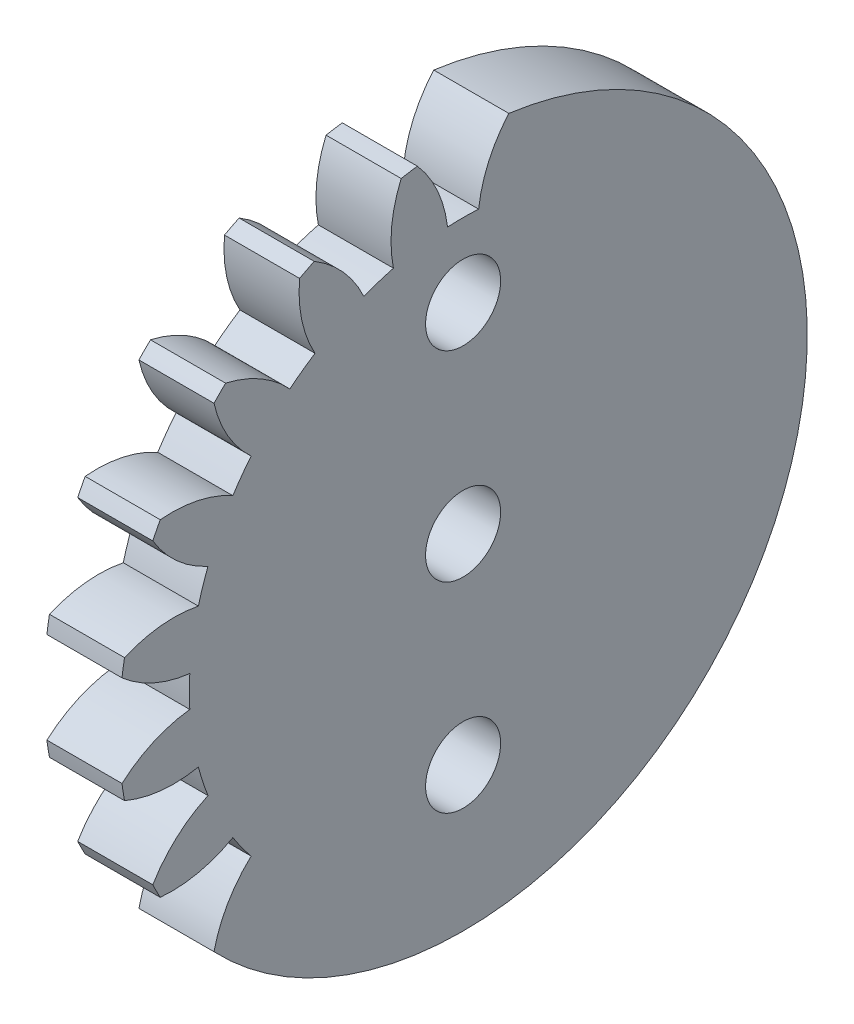
SolidWorks part; units mm, degrees
ref_plane "Plane1" through (0, 0, 0) normal (0, 0, 1) x (1, 0, 0)
ref_plane "Plane2" through (0, 0, 0) normal (0, 1, 0) x (1, 0, 0)
ref_plane "Plane3" through (0, 0, 0) normal (1, 0, 0) x (0, 0, -1)
sketch "HoldingSke" plane through (0, 0, 0) normal (0, 1, 0) x (1, 0, 0)
  line L0 (0, 0) -> (0.7518, -0.2736)
  line L1 (-15, 0) -> (100, 0) construction
  line L2 (0, 0) -> (-2.1039, 2.3779)
  line L3 (0, 0) -> (-11.863, 4.5341)
  line L4 (0, 0) -> (8.1152, 2.9537)
  line L5 (0, 0) -> (-46.8476, -17.4728)
  line L6 (0, 0) -> (-9.9476, -6.7116)
  line L7 (-2.1039, 2.3779) -> (8.6586, 51.2059)
  line L8 (-76.2, 54.61) -> (-75.7, 54.61)
  line L9 (-71.009, 38.7566) -> (-53.1078, 45.2721)
  line L10 (-76.2, 71.12) -> (104.1128, 71.12)
  line L11 (0, 0) -> (-12, 0)
  line L12 (-76.2, 101.6) -> (-76.155, 101.6)
  line L13 (24.9733, 27.94) -> (52.9518, 28.4284)
  line L14 (24.9733, 27.94) -> (24.9743, 27.94)
  line L15 (24.9733, 27.94) -> (100.4006, 29.5858)
  line L16 (-63.627, -1.25) -> (-12.827, -1.25)
  circle A0 centre (0, 0) radius 1.5
  circle A1 centre (0, 0) radius 10.9365
  circle A2 centre (0, 0) radius 37.5
  circle A3 centre (0, 0) radius 1.5
  dimension "Num_teeth" = 20
  dimension "Pitch_radius" = 180.3128
  dimension "Width" = 12
sketch "BasProSke" plane through (0, 0, 0) normal (0, 1, 0) x (1, 0, 0)
  line L0 (-10, 0) -> (60, 0) construction
  line L1 (0, 0) -> (0, 13.75)
  line L2 (0, 0) -> (3, 0)
  line L3 (3, 0) -> (3, 13.75)
  line L4 (3, 13.75) -> (0, 13.75)
  dimension "Thickness" = 3
  dimension "Diameter" = 27.5
revolve "Base-Revolve" add sketch "BasProSke" angle 360 about L0
sketch "TooCutSke" plane through (0, 0, 0) normal (1, 0, 0) x (0, 0, -1)
  line L1 (0, 0) -> (0, 107) construction
  line L2 (0, 0) -> (-1.0594, 12.455) construction
  line L3 (0, 0) -> (-3.9007, 24.6278) construction
  line L4 (-1.0594, 12.455) -> (-1.9503, 12.3139) construction
  arc A0 (0.6211, 10.9188) -> (-0.6211, 10.9188) centre (0, 0) ccw
  arc A1 (1.8466, 13.6511) -> (-1.8466, 13.6511) centre (0, 0) ccw
  circle A2 centre (0, 0) radius 12.5 construction
  circle A3 centre (0, 0) radius 11.7462 construction
  arc A4 (-0.6211, 10.9188) -> (-1.8466, 13.6511) centre (-5.5866, 10.3326) ccw
  arc A5 (1.8466, 13.6511) -> (0.6211, 10.9188) centre (5.5866, 10.3326) ccw
extrude "ToothCut" cut sketch "TooCutSke" along normal through all
fillet "Breaks" [suppressed] radius 0.025 tangent propagation no
fillet "RootFillets" [suppressed] radius 0.3135
pattern_circular "TeethCuts" count 8 every 18 about axis through (-10, 0, 0) along (1, 0, 0) of "ToothCut"
sketch "HubNeaOneSke" plane through (0, 0, 0) normal (-1, 0, 0) x (0, 0, 1)
  circle A0 centre (0, 0) radius 10.9365
  dimension "Diameter" = 21.873
extrude "HubNearOne" [suppressed] add sketch "HubNeaOneSke" along normal blind 47.0001
sketch "HubNeaBotSke" plane through (0, 0, 0) normal (-1, 0, 0) x (0, 0, 1)
  circle A0 centre (0, 0) radius 10.9365
  dimension "Diameter" = 21.873
extrude "HubNearBoth" [suppressed] add sketch "HubNeaBotSke" along normal blind 23.5
ref_plane "FarPln" through (3, 0, 0) normal (1, 0, 0) x (0, 0, -1)
sketch "HubFarSke" plane through (3, 0, 0) normal (1, 0, 0) x (0, 0, -1)
  circle A0 centre (0, 0) radius 10.9365
  dimension "Diameter" = 21.873
extrude "HubFar" [suppressed] add sketch "HubFarSke" along normal blind 23.5
sketch "BorSke" plane through (0, 0, 0) normal (1, 0, 0) x (0, 0, -1)
  circle A0 centre (0, 0) radius 1.5
  dimension "Diameter" = 3
extrude "Bore" cut sketch "BorSke" along normal mid plane 100.0001
sketch "KeySke" plane through (0, 0, 0) normal (1, 0, 0) x (0, 0, -1)
  line L0 (-0.6, 0) -> (-0.6, 2)
  line L1 (-0.6, 2) -> (0.6, 2)
  line L2 (0.6, 2) -> (0.6, 0)
  line L3 (0, 0) -> (0, 34) construction
  line L4 (-0.6, 0) -> (0.6, 0)
extrude "Keyway" [suppressed] cut sketch "KeySke" along normal mid plane 100.0001
sketch "草圖2" plane through (0, 0, 0) normal (-1, 0, 0) x (0, 0, 1)
  line L0 (0, 8) -> (0, -8)
  circle A0 centre (0, -8) radius 1.5
  circle A1 centre (0, 8) radius 1.5
  point P5 (0, 0)
  dimension "D2" = 3
  dimension "D3" = 3
  dimension "D1" = 16
extrude "除料-伸長2" cut sketch "草圖2" against normal blind 7 contours A0 | A1 region at (0, -6.9693, 1.0307) region at (0, 9.0307, -1.0307)
equation "' \"Module@HoldingSke\" = 6.35"
equation "' \"Num_teeth@HoldingSke\" = 12"
equation "' \"Ap@HoldingSke\" =  20"
equation "' \"Ap@HoldingSke\" = 20"
equation "' \"Width@HoldingSke\" = 0.5 * 25.4"
equation "' \"Hub_dia@HoldingSke\"= 1 * 25.4"
equation "' \"Hub_dia@HoldingSke\" = 1 * 25.4"
equation "' \"Overall_len@HoldingSke\" = 1.0 * 25.4"
equation "' \"Bore@HoldingSke\" = 0.75 * 25.4"
equation "' \"T_dim@HoldingSke\" = 0.1 * 25.4"
equation "' \"Width@KeySke\" = 0.25 * 25.4"
equation "' \"Show_teeth@HoldingSke\" = 13"
equation "' \"Backlash@HoldingSke\" = 0.009 * 25.4"
equation "' \"Addendum_fac@HoldingSke\" = 1.0"
equation "' \"Dedendum_fac@HoldingSke\" = 1.25"
equation "' \"Dedendum_add@HoldingSke\" = 0.00005 * 25.4"
equation "' \"Clearance_fac@HoldingSke\" = 0.25"
equation "\"Pitch@HoldingSke\" = 1 / \"Module@HoldingSke\""
equation "\"Overcut_dia@TooCutSke\" = (\"Num_teeth@HoldingSke\" + 2 * \"Addendum_fac@HoldingSke\") / \"Pitch@HoldingSke\" + 0.002 * 25.4"
equation "\"Pitch_dia@TooCutSke\" = \"Num_teeth@HoldingSke\" / \"Pitch@HoldingSke\""
equation "\"Base_dia@TooCutSke\" = \"Num_teeth@HoldingSke\" / \"Pitch@HoldingSke\" * cos((\"Ap@HoldingSke\"  * 3.14159265 / 180))"
equation "\"Root_dia@TooCutSke\" = (\"Num_teeth@HoldingSke\" + 2) / \"Pitch@HoldingSke\" - 2 * (\"Addendum_fac@HoldingSke\" + \"Dedendum_fac@HoldingSke\") / \"Pitch@HoldingSke\" - \"Dedendum_add@HoldingSke\" * 2"
equation "\"Half_ang@TooCutSke\" = 180 / \"Num_teeth@HoldingSke\""
equation "\"Half_CT@TooCutSke\" = \"Num_teeth@HoldingSke\" / \"Pitch@HoldingSke\" * sin((3.14159265 / 2 / \"Num_teeth@HoldingSke\")) / 2 - 7 * \"Backlash@HoldingSke\" / 4"
equation "\"Flank_rad@TooCutSke\" = \"Num_teeth@HoldingSke\" / \"Pitch@HoldingSke\" / 5"
equation "\"Radius@RootFillets\" = \"Clearance_fac@HoldingSke\" / \"Pitch@HoldingSke\" + \"Dedendum_add@HoldingSke\""
equation "\"Break_rad@Breaks\" = 0.02 / \"Pitch@HoldingSke\""
equation "\"Thickness@HoldingSke\" = \"Width@HoldingSke\""
equation "\"OAL@HoldingSke\" = \"Thickness@HoldingSke\""
equation "\"MHD@HoldingSke\" = (\"Num_teeth@HoldingSke\" + 2) / \"Pitch@HoldingSke\" - 2 * (\"Addendum_fac@HoldingSke\" + \"Dedendum_fac@HoldingSke\")  / \"Pitch@HoldingSke\" - \"Dedendum_add@HoldingSke\" * 2"
equation "\"MBD@HoldingSke\" = (\"Num_teeth@HoldingSke\" + 2) / \"Pitch@HoldingSke\" - 2 * (\"Addendum_fac@HoldingSke\" + \"Dedendum_fac@HoldingSke\")  / \"Pitch@HoldingSke\" - \"Dedendum_add@HoldingSke\" * 2 - 0.002 * 25.4"
equation "\"MHD@HoldingSke\" = ((sgn( \"MHD@HoldingSke\" - \"Hub_dia@HoldingSke\" )-1)*( \"MHD@HoldingSke\" - \"Hub_dia@HoldingSke\" ))/-2+ \"Hub_dia@HoldingSke\""
equation "\"MBD@HoldingSke\" = ((sgn( \"MBD@HoldingSke\" - \"Bore@HoldingSke\" )-1)*( \"MBD@HoldingSke\" - \"Bore@HoldingSke\" ))/-2+ \"Bore@HoldingSke\""
equation "\"OAL@HoldingSke\" = ((sgn( \"OAL@HoldingSke\" - \"Overall_len@HoldingSke\" )+1)*( \"OAL@HoldingSke\" - \"Overall_len@HoldingSke\" ))/2 + \"Overall_len@HoldingSke\" + 0.000002 * 25.4"
equation "\"Num_teeth@TeethCuts\" = ((sgn( \"Num_teeth@TeethCuts\" - \"Num_teeth@HoldingSke\" )-1)*( \"Num_teeth@TeethCuts\" - \"Num_teeth@HoldingSke\" ))/-2+ \"Num_teeth@HoldingSke\""
equation "\"Num_teeth@TeethCuts\" = ((sgn( \"Num_teeth@TeethCuts\" - 2.0)+1)*( \"Num_teeth@TeethCuts\" - 2.0))/2 +2.0"
equation "\"Diameter@BasProSke\" = (\"Num_teeth@HoldingSke\" + 2 * \"Addendum_fac@HoldingSke\") / \"Pitch@HoldingSke\""
equation "' \"Fillet_rad@BasProSke\" =  \"Thickness@HoldingSke\" * 0.05"
equation "' \"Fillet_rad@BasProSke\" = \"Thickness@HoldingSke\" * 0.05"
equation "\"MHD@HoldingSke\" = ((sgn( \"MHD@HoldingSke\" - \"Root_dia@TooCutSke\" )-1)*( \"MHD@HoldingSke\" - \"Root_dia@TooCutSke\" ))/-2+ \"Root_dia@TooCutSke\""
equation "\"Diameter@HubNeaOneSke\" = \"MHD@HoldingSke\""
equation "\"Length@HubNearOne\" = \"OAL@HoldingSke\" - \"Thickness@BasProSke\""
equation "\"Diameter@HubNeaBotSke\" = \"MHD@HoldingSke\""
equation "\"Length@HubNearBoth\" = ( \"OAL@HoldingSke\" - \"Thickness@BasProSke\" ) / 2.0"
equation "\"Thickness@FarPln\" = \"Thickness@BasProSke\""
equation "\"Diameter@HubFarSke\" = \"MHD@HoldingSke\""
equation "\"Length@HubFar\" = ( \"OAL@HoldingSke\" - \"Thickness@BasProSke\" ) / 2.0"
equation "\"Diameter@BorSke\" = \"MBD@HoldingSke\""
equation "\"D1@Bore\" = \"OAL@HoldingSke\" * 2.0"
equation "\"D1@Keyway\" = \"OAL@HoldingSke\" * 2.0"
equation "\"Offset@KeySke\" = \"T_dim@HoldingSke\" + \"MBD@HoldingSke\" / 2.0"
